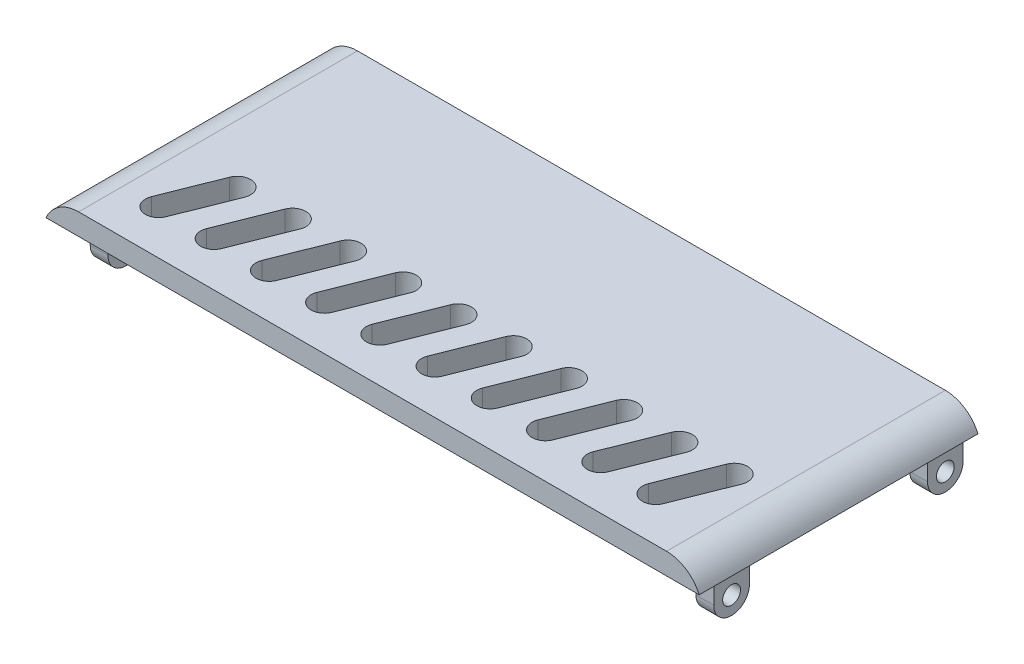
SolidWorks part; units mm, degrees
ref_plane "前视基准面" through (0, 0, 0) normal (0, 0, 1) x (1, 0, 0)
ref_plane "上视基准面" through (0, 0, 0) normal (0, 1, 0) x (1, 0, 0)
ref_plane "右视基准面" through (0, 0, 0) normal (1, 0, 0) x (0, 0, -1)
sketch "草图2" plane through (0, 0, 0) normal (0, 1, 0) x (1, 0, 0)
  line L1 (-31.0872, 19.8404) -> (42.9128, 19.8404)
  line L2 (-31.0872, 19.8404) -> (-31.0872, -11.4596)
  line L3 (-31.0872, -11.4596) -> (42.9128, -11.4596)
  line L4 (42.9128, 19.8404) -> (42.9128, -11.4596)
  point P4 (0, 0)
  dimension "D1" = 74
  dimension "D2" = 31.3
extrude "凸台-拉伸1" add sketch "草图2" along normal blind 4
fillet "圆角1" radius 4 2 edges at (-31.0872, 4, -4.1904) (42.9128, 4, -4.1904)
sketch "草图3" plane through (0, 0, -19.8404) normal (0, 0, -1) x (-1, 0, 0)
  line L1 (31.0872, 0) -> (-42.9128, 0)
  line L2 (31.0872, 0) -> (31.0872, 1.6)
  line L3 (31.0872, 1.6) -> (-42.9128, 1.6)
  line L4 (-42.9128, 0) -> (-42.9128, 1.6)
  dimension "D1" = 1.6
extrude "切除-拉伸1" cut sketch "草图3" against normal through all
sketch "草图19" plane through (0, 4, 0) normal (0, 1, 0) x (1, 0, 0)
  line L0 (-20.5872, -0.1596) -> (-23.0872, -6.4596) construction
  line L5 (-19.1929, -0.7128) -> (-21.6929, -7.0128)
  line L8 (-21.9814, 0.3937) -> (-24.4814, -5.9063)
  line L11 (38.9128, 19.8404) -> (-27.0872, 19.8404) construction
  line L14 (-27.0872, -11.4596) -> (38.9128, -11.4596) construction
  line L17 (-14.3872, -0.1596) -> (-16.8872, -6.4596) construction
  line L20 (-12.9929, -0.7128) -> (-15.4929, -7.0128)
  line L23 (-15.7814, 0.3937) -> (-18.2814, -5.9063)
  line L26 (-40.9597, 4.1904) -> (-18.0872, 4.1904) construction
  line L27 (-27.0872, 19.8404) -> (-27.0872, -11.4596) construction
  line L28 (-8.1872, -0.1596) -> (-10.6872, -6.4596) construction
  line L31 (-6.7929, -0.7128) -> (-9.2929, -7.0128)
  line L34 (-9.5814, 0.3937) -> (-12.0814, -5.9063)
  line L37 (-1.9872, -0.1596) -> (-4.4872, -6.4596) construction
  line L40 (-0.5929, -0.7128) -> (-3.0929, -7.0128)
  line L43 (-3.3814, 0.3937) -> (-5.8814, -5.9063)
  line L46 (4.2128, -0.1596) -> (1.7128, -6.4596) construction
  line L49 (5.6071, -0.7128) -> (3.1071, -7.0128)
  line L52 (2.8186, 0.3937) -> (0.3186, -5.9063)
  line L53 (10.4128, -0.1596) -> (7.9128, -6.4596) construction
  line L54 (11.8071, -0.7128) -> (9.3071, -7.0128)
  line L55 (9.0186, 0.3937) -> (6.5186, -5.9063)
  line L56 (16.6128, -0.1596) -> (14.1128, -6.4596) construction
  line L57 (18.0071, -0.7128) -> (15.5071, -7.0128)
  line L58 (15.2186, 0.3937) -> (12.7186, -5.9063)
  line L59 (22.8128, -0.1596) -> (20.3128, -6.4596) construction
  line L60 (24.2071, -0.7128) -> (21.7071, -7.0128)
  line L61 (21.4186, 0.3937) -> (18.9186, -5.9063)
  line L62 (29.0128, -0.1596) -> (26.5128, -6.4596) construction
  line L63 (30.4071, -0.7128) -> (27.9071, -7.0128)
  line L64 (27.6186, 0.3937) -> (25.1186, -5.9063)
  line L65 (35.2128, -0.1596) -> (32.7128, -6.4596) construction
  line L66 (36.6071, -0.7128) -> (34.1071, -7.0128)
  line L67 (33.8186, 0.3937) -> (31.3186, -5.9063)
  arc A32 (-19.1929, -0.7128) -> (-21.9814, 0.3937) centre (-20.5872, -0.1596) ccw
  arc A33 (-24.4814, -5.9063) -> (-21.6929, -7.0128) centre (-23.0872, -6.4596) ccw
  arc A34 (-12.9929, -0.7128) -> (-15.7814, 0.3937) centre (-14.3872, -0.1596) ccw
  arc A35 (-18.2814, -5.9063) -> (-15.4929, -7.0128) centre (-16.8872, -6.4596) ccw
  arc A36 (-6.7929, -0.7128) -> (-9.5814, 0.3937) centre (-8.1872, -0.1596) ccw
  arc A37 (-12.0814, -5.9063) -> (-9.2929, -7.0128) centre (-10.6872, -6.4596) ccw
  arc A38 (-0.5929, -0.7128) -> (-3.3814, 0.3937) centre (-1.9872, -0.1596) ccw
  arc A39 (-5.8814, -5.9063) -> (-3.0929, -7.0128) centre (-4.4872, -6.4596) ccw
  arc A40 (5.6071, -0.7128) -> (2.8186, 0.3937) centre (4.2128, -0.1596) ccw
  arc A41 (0.3186, -5.9063) -> (3.1071, -7.0128) centre (1.7128, -6.4596) ccw
  arc A42 (11.8071, -0.7128) -> (9.0186, 0.3937) centre (10.4128, -0.1596) ccw
  arc A43 (6.5186, -5.9063) -> (9.3071, -7.0128) centre (7.9128, -6.4596) ccw
  arc A44 (18.0071, -0.7128) -> (15.2186, 0.3937) centre (16.6128, -0.1596) ccw
  arc A45 (12.7186, -5.9063) -> (15.5071, -7.0128) centre (14.1128, -6.4596) ccw
  arc A46 (24.2071, -0.7128) -> (21.4186, 0.3937) centre (22.8128, -0.1596) ccw
  arc A47 (18.9186, -5.9063) -> (21.7071, -7.0128) centre (20.3128, -6.4596) ccw
  arc A48 (30.4071, -0.7128) -> (27.6186, 0.3937) centre (29.0128, -0.1596) ccw
  arc A49 (25.1186, -5.9063) -> (27.9071, -7.0128) centre (26.5128, -6.4596) ccw
  arc A50 (36.6071, -0.7128) -> (33.8186, 0.3937) centre (35.2128, -0.1596) ccw
  arc A51 (31.3186, -5.9063) -> (34.1071, -7.0128) centre (32.7128, -6.4596) ccw
  point P2 (-21.8372, -3.3096)
  point P15 (-15.6372, -3.3096)
  point P22 (-9.4372, -3.3096)
  point P29 (-3.2372, -3.3096)
  point P36 (2.9628, -3.3096)
  point P43 (9.1628, -3.3096)
  point P50 (15.3628, -3.3096)
  point P57 (21.5628, -3.3096)
  point P64 (-27.0872, 4.1904)
  point P68 (27.7628, -3.3096)
  point P75 (33.9628, -3.3096)
  dimension "D6" = 4
  dimension "D3" = 1.5
  dimension "D1" = 20
  dimension "D2" = 5
  dimension "D4" = 6.5
  dimension "D5" = 10
extrude "切除-拉伸6" cut sketch "草图19" against normal up to next
sketch "草图22" plane through (0, 1.6, 0) normal (0, -1, 0) x (1, 0, 0)
  line L0 (-30.7532, 11.4596) -> (42.5789, 11.4596) construction
  line L1 (-29.0872, 8.1596) -> (-27.0872, 8.1596)
  line L2 (-29.0872, 8.1596) -> (-29.0872, 4.1596)
  line L3 (-29.0872, 4.1596) -> (-27.0872, 4.1596)
  line L4 (-27.0872, 8.1596) -> (-27.0872, 4.1596)
  line L5 (-29.0872, 11.4596) -> (-29.0872, 1.1198) construction
  line L6 (-30.7532, -19.8404) -> (42.5789, -19.8404) construction
  line L7 (-27.0872, -19.8404) -> (-29.0872, -19.8404)
  line L8 (-27.0872, -19.8404) -> (-27.0872, -15.8404)
  line L9 (-27.0872, -15.8404) -> (-29.0872, -15.8404)
  line L10 (-29.0872, -19.8404) -> (-29.0872, -15.8404)
  line L11 (-29.0872, -5.8802) -> (-29.0872, -19.8404) construction
  line L12 (40.9128, 1.1198) -> (40.9128, 11.4596) construction
  line L13 (40.9128, 8.1596) -> (38.9128, 8.1596)
  line L14 (40.9128, 8.1596) -> (40.9128, 4.1596)
  line L15 (40.9128, 4.1596) -> (38.9128, 4.1596)
  line L16 (38.9128, 8.1596) -> (38.9128, 4.1596)
  line L18 (40.9128, -19.8404) -> (38.9128, -19.8404)
  line L19 (40.9128, -19.8404) -> (40.9128, -15.8404)
  line L20 (40.9128, -15.8404) -> (38.9128, -15.8404)
  line L21 (38.9128, -19.8404) -> (38.9128, -15.8404)
  dimension "D1" = 2
  dimension "D2" = 4
  dimension "D3" = 4
  dimension "D4" = 2
  dimension "D5" = 3.3
extrude "凸台-拉伸9" add sketch "草图22" along normal blind 5.5
fillet "圆角3" radius 2 8 edges at (-28.0872, -3.9, -19.8404) (-28.0872, -3.9, -15.8404) (-28.0872, -3.9, 4.1596) (-28.0872, -3.9, 8.1596) (39.9128, -3.9, -19.8404) (39.9128, -3.9, -15.8404) (39.9128, -3.9, 4.1596) (39.9128, -3.9, 8.1596)
sketch "草图23" plane through (-29.0872, 0, 0) normal (-1, 0, 0) x (0, 0, 1)
  circle A0 centre (6.1596, -1.9) radius 1
  circle A1 centre (-17.8404, -1.9) radius 1
  arc A2 (-17.8404, -3.9) -> (-15.8404, -1.9) centre (-17.8404, -1.9) ccw construction
  arc A3 (6.1596, -3.9) -> (8.1596, -1.9) centre (6.1596, -1.9) ccw construction
  dimension "D1" = 2
  dimension "D2" = 2
extrude "切除-拉伸9" cut sketch "草图23" against normal blind 2 draft 4
sketch "草图24" plane through (0, 1.6, 0) normal (0, -1, 0) x (1, 0, 0)
  line L0 (-30.7532, 11.4596) -> (42.5789, 11.4596) construction
  line L1 (-18.7532, 10.0596) -> (-14.7532, 10.0596)
  line L2 (-18.7532, 10.0596) -> (-18.7532, 8.0596)
  line L3 (-18.7532, 8.0596) -> (-14.7532, 8.0596)
  line L4 (-14.7532, 10.0596) -> (-14.7532, 8.0596)
  line L5 (30.5789, 8.0596) -> (26.5789, 8.0596)
  line L6 (30.5789, 8.0596) -> (30.5789, 10.0596)
  line L7 (30.5789, 10.0596) -> (26.5789, 10.0596)
  line L8 (26.5789, 8.0596) -> (26.5789, 10.0596)
  line L9 (42.5789, -19.8404) -> (42.5789, 11.4596) construction
  line L10 (-30.7532, 11.4596) -> (-30.7532, -19.8404) construction
  dimension "D1" = 3.4
  dimension "D2" = 2
  dimension "D3" = 12
  dimension "D4" = 4
  dimension "D5" = 12
  dimension "D6" = 4
extrude "凸台-拉伸10" add sketch "草图24" along normal blind 0.2
sketch "草图25" plane through (0, 1.6, 0) normal (0, -1, 0) x (1, 0, 0)
  text T0 "WHISPLAY" font "@Adobe Gothic Std B" height 3.5
extrude "切除-拉伸10" cut sketch "草图25" against normal blind 0.4
sketch "草图26" plane through (40.9128, 0, 0) normal (1, 0, 0) x (0, 0, -1)
  circle A1 centre (17.8404, -1.9) radius 1
  circle A2 centre (17.8404, -1.9) radius 1
  circle A3 centre (-6.1596, -1.9) radius 1
  circle A4 centre (-6.1596, -1.9) radius 1
  dimension "D1" = 0
  dimension "D2" = 0
extrude "切除-拉伸11" cut sketch "草图26" against normal blind 2 draft 4
sketch "草图27" plane through (0, 1.6, 0) normal (0, -1, 0) x (1, 0, 0)
  line L0 (-30.7532, 11.4596) -> (42.5789, 11.4596) construction
  line L1 (-27.0872, 7.4732) -> (-24.1928, 7.4732)
  line L2 (-27.0872, 7.4732) -> (-27.0872, 8.1596)
  line L3 (-27.0872, 8.1596) -> (-24.1928, 8.1596)
  line L4 (-24.1928, 7.4732) -> (-24.1928, 8.1596)
  line L5 (-27.0872, 13.4596) -> (-27.0872, -21.8404) construction
  line L6 (38.9128, 7.4732) -> (33.8185, 7.4732)
  line L7 (38.9128, 7.4732) -> (38.9128, 8.1596)
  line L8 (38.9128, 8.1596) -> (33.8185, 8.1596)
  line L9 (33.8185, 7.4732) -> (33.8185, 8.1596)
  line L11 (38.9128, 8.1596) -> (38.9128, 6.1596) construction
  arc A0 (-21.6929, 7.0128) -> (-24.4814, 5.9063) centre (-23.0872, 6.4596) ccw construction
  arc A1 (34.1071, 7.0128) -> (31.3186, 5.9063) centre (32.7128, 6.4596) ccw construction
  dimension "D1" = 3.3
extrude "凸台-拉伸11" add sketch "草图27" along normal blind 3
chamfer "倒角1" distance 1 angle 45 2 edges at (-25.64, -1.4, 8.1596) (36.3657, -1.4, 8.1596)
